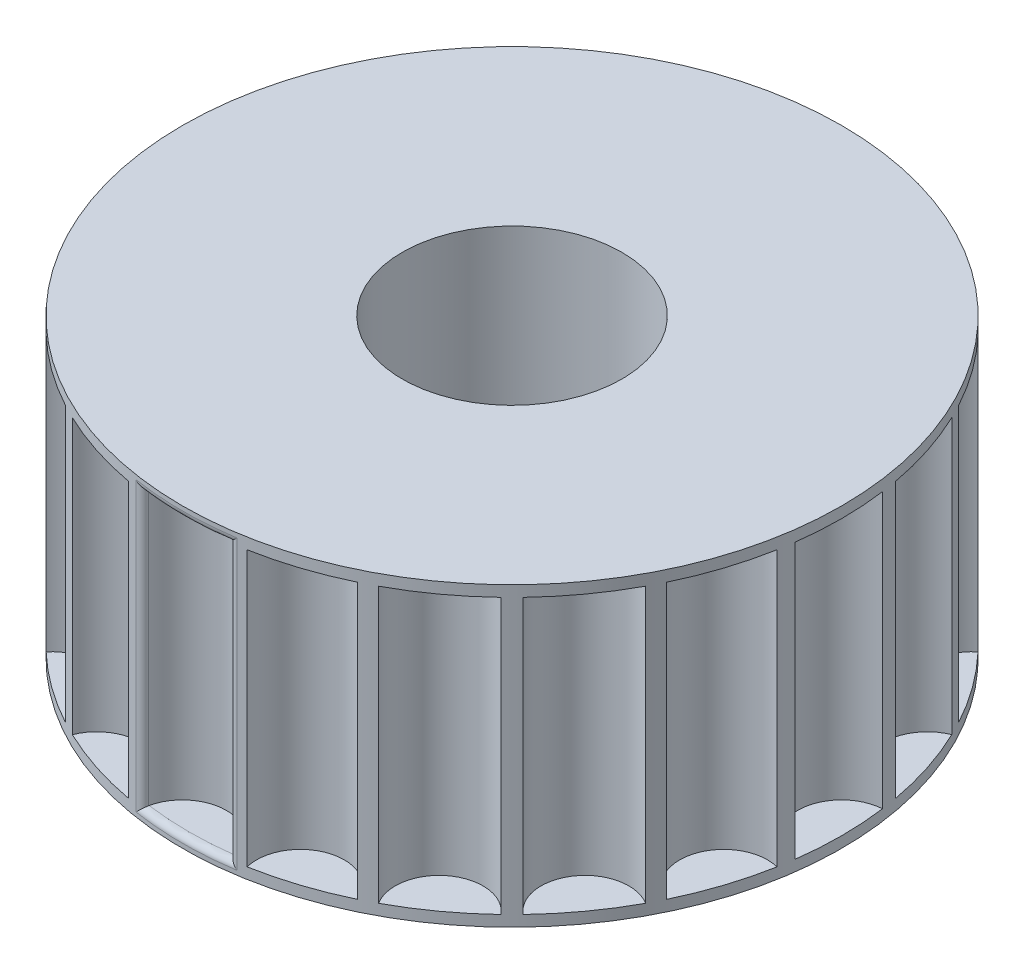
SolidWorks part; units mm, degrees
ref_plane "前视基准面" through (0, 0, 0) normal (0, 0, 1) x (1, 0, 0)
ref_plane "上视基准面" through (0, 0, 0) normal (0, 1, 0) x (1, 0, 0)
ref_plane "右视基准面" through (0, 0, 0) normal (1, 0, 0) x (0, 0, -1)
sketch "草图2" plane through (0, 0, 0) normal (0, 1, 0) x (1, 0, 0)
  circle A0 centre (0, 0) radius 15
  dimension "D1" = 30
extrude "凸台-拉伸1" add sketch "草图2" along normal blind 13
sketch "草图3" plane through (0, 13, 0) normal (0, 1, 0) x (1, 0, 0)
  circle A0 centre (0, 0) radius 12
  dimension "D1" = 24
sketch "草图8" plane through (0, 0, 0) normal (0, -1, 0) x (1, 0, 0)
  circle A0 centre (0, 15) radius 2
  dimension "D1" = 4
  dimension "D2" = 15
extrude "切除-拉伸10" cut sketch "草图8" against normal blind 12.5 contours A0
sketch "草图10" plane through (0, 0, 0) normal (0, -1, 0) x (1, 0, 0)
  circle A0 centre (0, 0) radius 15
  dimension "D1" = 30
extrude "凸台-拉伸4" add sketch "草图10" along normal blind 0.5 contours A0
sketch "草图11" plane through (0, -0.5, 0) normal (0, -1, 0) x (1, 0, 0)
  circle A0 centre (0, 0) radius 12
  dimension "D1" = 24
extrude "凸台-拉伸5" add sketch "草图11" along normal blind 0.5
sketch "草图12" plane through (0, -1, 0) normal (0, -1, 0) x (1, 0, 0)
  circle A0 centre (0, 0) radius 5
  dimension "D1" = 10
extrude "切除-拉伸12" cut sketch "草图12" against normal through all
fillet "圆角2" radius 0.3 4 edges at (-1.9956, 6.25, 14.8667) (0, 0, 15) (1.9956, 6.25, 14.8667) (0, 12.5, 15)
pattern_circular "阵列(圆周)1" count 20 every 18 about axis through (0, 13, 0) along (0, -1, 0) of "切除-拉伸10"
